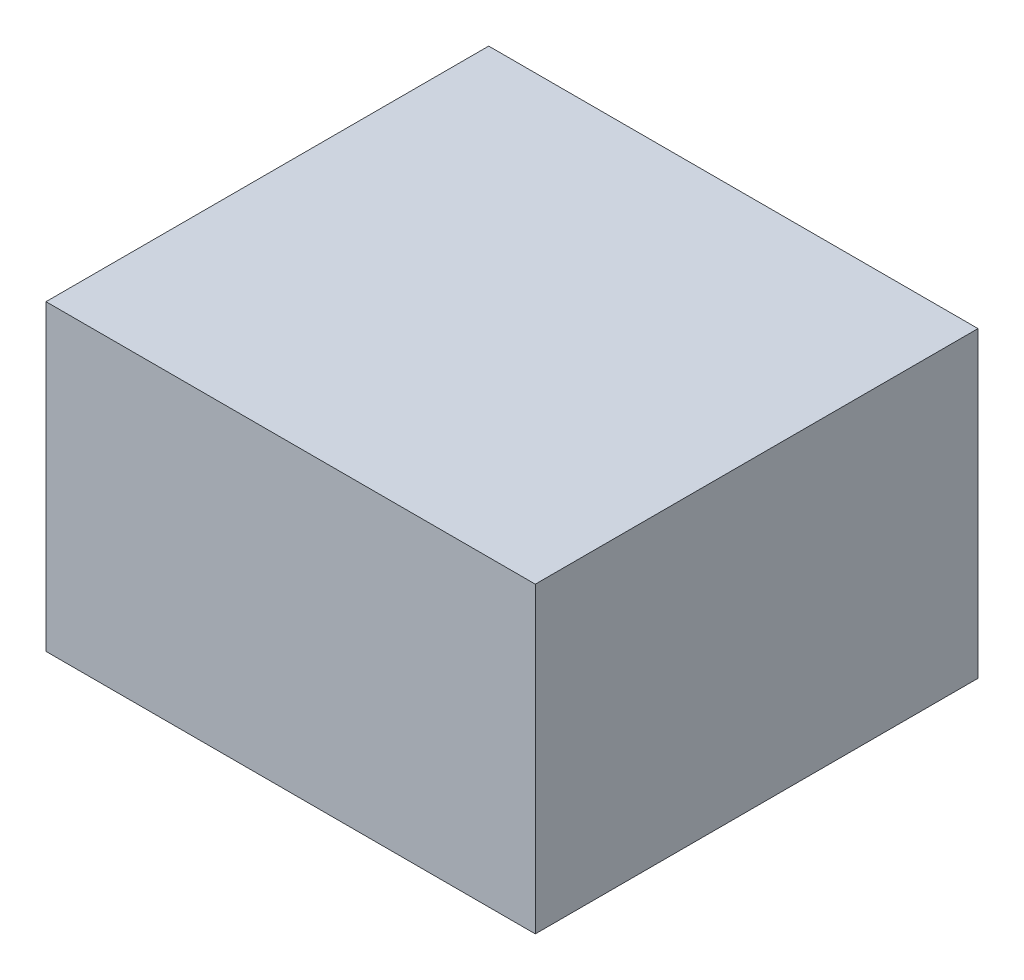
SolidWorks part; units mm, degrees
ref_plane "前视基准面" through (0, 0, 0) normal (0, 0, 1) x (1, 0, 0)
ref_plane "上视基准面" through (0, 0, 0) normal (0, 1, 0) x (1, 0, 0)
ref_plane "右视基准面" through (0, 0, 0) normal (1, 0, 0) x (0, 0, -1)
other "Configuration Table"
sketch "草图1" plane through (0, 0, 0) normal (0, 0, 1) x (1, 0, 0)
  line L1 (-21, -13) -> (21, -13)
  line L2 (-21, -13) -> (-21, 13)
  line L3 (-21, 13) -> (21, 13)
  line L4 (21, -13) -> (21, 13)
  line L5 (-21, -13) -> (21, 13) construction
  line L6 (-21, 13) -> (21, -13) construction
  point P0 (0, 0)
extrude "凸台-拉伸1" add sketch "草图1" along normal mid plane 38
